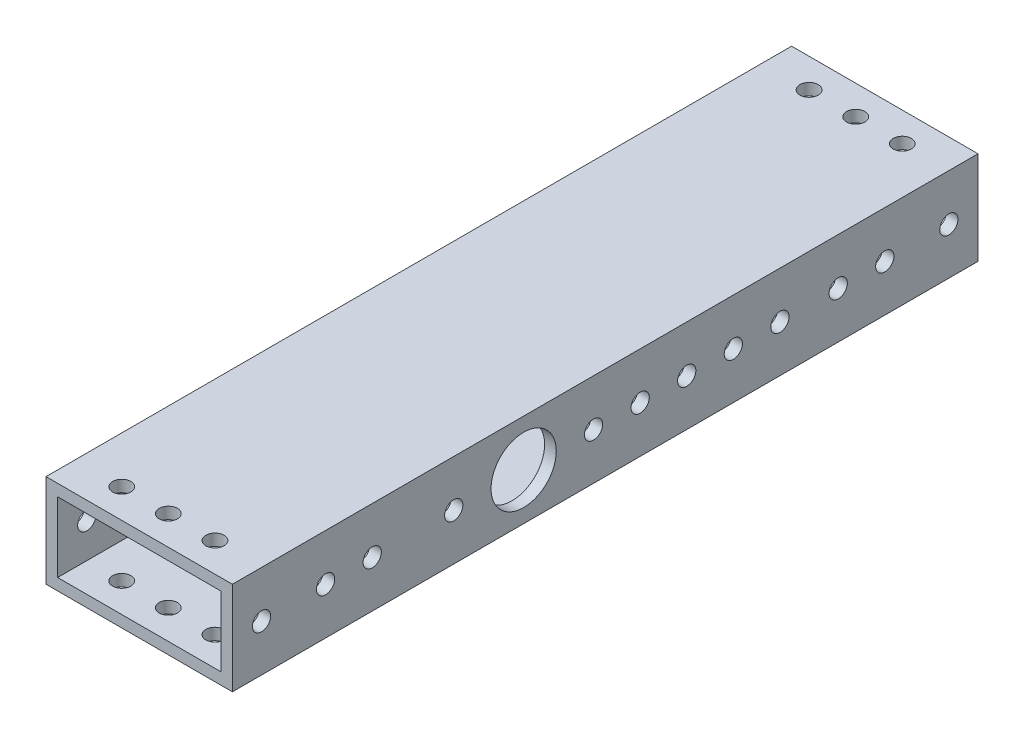
SolidWorks part; units mm, degrees
material "6061-T6 (SS)"
ref_plane "Front Plane" through (0, 0, 0) normal (0, 0, 1) x (1, 0, 0)
ref_plane "Top Plane" through (0, 0, 0) normal (0, 1, 0) x (1, 0, 0)
ref_plane "Right Plane" through (0, 0, 0) normal (1, 0, 0) x (0, 0, -1)
sketch "Sketch1" plane through (0, 0, 0) normal (0, 0, 1) x (1, 0, 0)
  line L0 (-22.225, 9.525) -> (22.225, 9.525)
  line L1 (-25.4, -12.7) -> (25.4, -12.7)
  line L2 (-25.4, -12.7) -> (-25.4, 12.7)
  line L3 (-25.4, 12.7) -> (25.4, 12.7)
  line L4 (25.4, -12.7) -> (25.4, 12.7)
  line L5 (-25.4, -12.7) -> (25.4, 12.7) construction
  line L6 (-25.4, 12.7) -> (25.4, -12.7) construction
  line L7 (22.225, -9.525) -> (22.225, 9.525)
  line L8 (-22.225, -9.525) -> (22.225, -9.525)
  line L9 (-22.225, -9.525) -> (-22.225, 9.525)
  point P0 (0, 0)
  dimension "D1" = 50.8
  dimension "D2" = 25.4
  dimension "D3" = 3.175
extrude "Boss-Extrude1" add sketch "Sketch1" along normal mid plane 203.2
sketch "Sketch3" plane through (0, 12.7, 0) normal (0, 1, 0) x (1, 0, 0)
  line L0 (-25.4, 0) -> (25.4, 0) construction
  line L1 (-25.4, -101.6) -> (-25.4, 101.6) construction
  line L2 (25.4, -101.6) -> (25.4, 101.6) construction
  line L3 (25.4, -101.6) -> (-25.4, -101.6) construction
  circle A0 centre (-12.7, -93.6625) radius 2.4892
  circle A1 centre (0, -93.6625) radius 2.4892
  circle A2 centre (12.7, -93.6625) radius 2.4892
  circle A3 centre (12.7, 93.6625) radius 2.4892
  circle A4 centre (0, 93.6625) radius 2.4892
  circle A5 centre (-12.7, 93.6625) radius 2.4892
  dimension "D1" = 4.9784
  dimension "D2" = 12.7
  dimension "D3" = 12.7
  dimension "D4" = 7.9375
extrude "Cut-Extrude2" cut sketch "Sketch3" against normal through all
sketch "Sketch4" plane through (25.4, 0, 0) normal (1, 0, 0) x (0, 0, -1)
  line L0 (-22.225, 0) -> (-45.1908, 0) construction
  line L1 (-13.335, 0) -> (-31.115, 0) construction
  line L8 (-22.225, 0) -> (34.925, 0) construction
  line L9 (0, 12.7) -> (0, -12.7) construction
  line L10 (-101.6, 12.7) -> (101.6, 12.7) construction
  line L11 (-101.6, -12.7) -> (101.6, -12.7) construction
  circle A0 centre (-22.225, 0) radius 8.89
  circle A9 centre (34.925, 0) radius 2.4892
  circle A10 centre (22.225, 0) radius 2.4892
  dimension "D2" = 17.78
  dimension "D3" = 22.225
  dimension "D1" = 57.15
  dimension "D4" = 4.9784
  dimension "D6" = 44.45
extrude "Cut-Extrude3" cut sketch "Sketch4" against normal through all contours A0 | A9 | A10
sketch "Sketch2" plane through (25.4, 0, 0) normal (1, 0, 0) x (0, 0, -1)
  line L0 (-101.6, -12.7) -> (-101.6, 12.7) construction
  line L1 (0, 12.7) -> (0, -12.7) construction
  line L2 (-101.6, 12.7) -> (101.6, 12.7) construction
  line L3 (-101.6, -12.7) -> (101.6, -12.7) construction
  circle A0 centre (-93.6625, 0) radius 2.4892
  circle A1 centre (93.6625, 0) radius 2.4892
  circle A2 centre (-76.2, 0) radius 2.4892
  circle A3 centre (-63.5, 0) radius 2.4892
  circle A4 centre (63.5, 0) radius 2.4892
  circle A5 centre (76.2, 0) radius 2.4892
  dimension "D2" = 4.9784
  dimension "D5" = 4.9784
  dimension "D4" = 25.4
  dimension "D1" = 7.9375
  dimension "D3" = 12.7
extrude "Cut-Extrude1" cut sketch "Sketch2" against normal through all
sketch "Sketch5" plane through (0, -12.7, 0) normal (0, -1, 0) x (1, 0, 0)
  line L0 (-25.4, 101.6) -> (-25.4, -101.6) construction
  line L1 (-25.4, 101.6) -> (25.4, 101.6) construction
  line L4 (25.4, 22.225) -> (-25.4, 22.225) construction
  line L5 (25.4, 101.6) -> (25.4, -101.6) construction
  circle A0 centre (-3.175, 66.675) radius 2.4892
  circle A1 centre (-15.875, 66.675) radius 2.4892
  circle A2 centre (-15.875, 53.975) radius 2.4892
  circle A3 centre (-3.175, 53.975) radius 2.4892
  circle A8 centre (-3.175, -9.525) radius 2.4892
  circle A9 centre (-15.875, -9.525) radius 2.4892
  circle A10 centre (-15.875, -22.225) radius 2.4892
  circle A11 centre (-3.175, -22.225) radius 2.4892
  dimension "D3" = 4.9784
  dimension "D4" = 9.525
  dimension "D7" = 12.7
  dimension "D12" = 79.375
  dimension "D5" = 31.75
  dimension "D6" = 12.7
  dimension "D1" = 2
  dimension "D2" = 2
extrude "Cut-Extrude4" cut sketch "Sketch5" against normal up to next
sketch "Sketch7" plane through (25.4, 0, 0) normal (1, 0, 0) x (0, 0, -1)
  circle A0 centre (47.625, 0) radius 2.4892
  circle A1 centre (34.925, 0) radius 2.4892 construction
  circle A5 centre (9.525, 0) radius 2.4892
  circle A6 centre (-3.175, 0) radius 2.4892
  circle A7 centre (-41.275, 0) radius 2.4892
  circle A8 centre (-22.225, 0) radius 8.89 construction
  dimension "D1" = 12.7
  dimension "D2" = 19.05
  dimension "D3" = 19.05
  dimension "D4" = 12.7
extrude "Cut-Extrude5" cut sketch "Sketch7" against normal up to next contours A0 | A7 | A6 | A5
